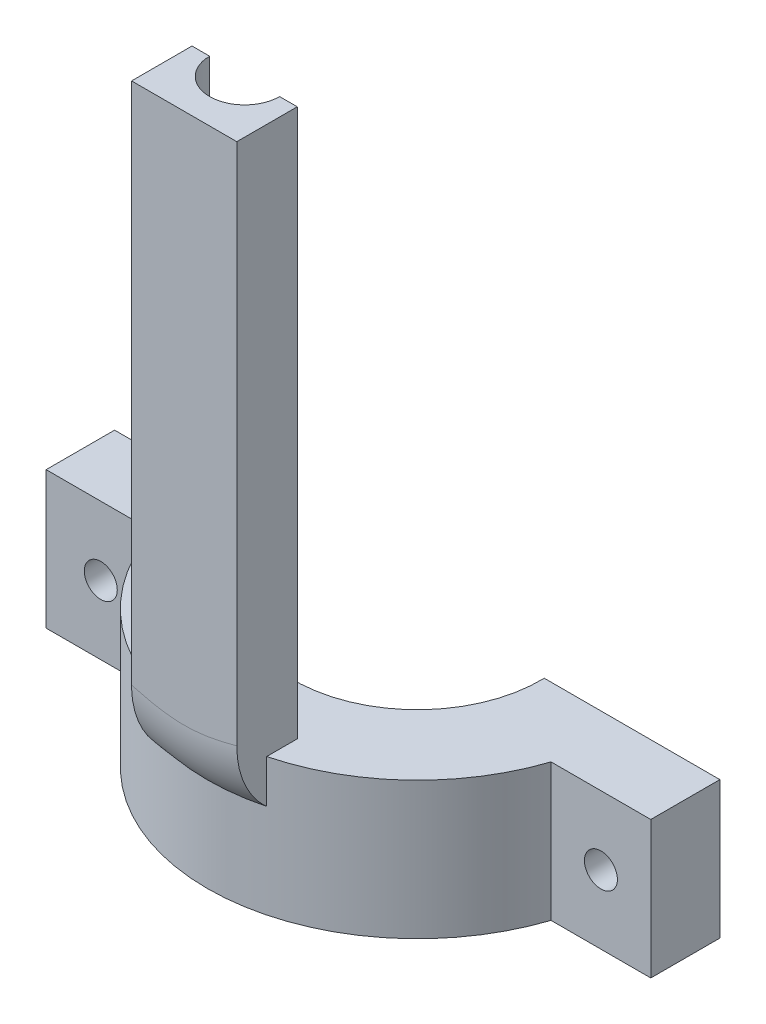
SolidWorks part; units mm, degrees
ref_plane "前基準面" through (0, 0, 0) normal (0, 0, 1) x (1, 0, 0)
ref_plane "上基準面" through (0, 0, 0) normal (0, 1, 0) x (1, 0, 0)
ref_plane "右基準面" through (0, 0, 0) normal (1, 0, 0) x (0, 0, -1)
sketch "草圖1" plane through (0, 0, 0) normal (0, 1, 0) x (1, 0, 0)
  circle A0 centre (0, 0) radius 14.32
  dimension "D1" = 28.64
extrude "伸長-薄件1" add sketch "草圖1" along normal blind 10 thin thin type one direction wall 10
ref_plane "平面1" through (0, 0, 25) normal (0, 0, 1) x (1, 0, 0)
sketch "草圖5" plane through (0, 0, 25) normal (0, 0, 1) x (1, 0, 0)
  line L0 (0, -990) -> (0, 49010) construction
  line L1 (14.32, 10) -> (-14.32, 10) construction
  line L2 (-1024.46, 5) -> (48975.54, 5) construction
  line L3 (-24.32, 10) -> (-24.32, 0) construction
  line L5 (-6.0941, 11.3789) -> (6.0941, 11.3789)
  line L6 (-6.0941, 11.3789) -> (-6.0941, 5)
  line L7 (-6.0941, 5) -> (6.0941, 5)
  line L8 (6.0941, 11.3789) -> (6.0941, 5)
  line L9 (-6.0941, 11.3789) -> (6.0941, 5) construction
  line L10 (-6.0941, 5) -> (6.0941, 11.3789) construction
  point P5 (0, 10)
  point P6 (0, 8.1895)
  point P10 (-24.32, 5)
  dimension "D1" = 0
extrude "填料-伸長3" add sketch "草圖5" along normal blind 5 and the other way blind 5
sketch "草圖6" plane through (0, 11.3789, 0) normal (0, 1, 0) x (1, 0, 0)
  line L1 (-6.0941, -20) -> (6.0941, -20)
  line L2 (-6.0941, -20) -> (-6.0941, -30)
  line L3 (-6.0941, -30) -> (6.0941, -30)
  line L4 (6.0941, -20) -> (6.0941, -30)
extrude "填料-伸長4" add sketch "草圖6" along normal blind 37
sketch "草圖8" plane through (0, 48.3789, 0) normal (0, 1, 0) x (1, 0, 0)
  line L1 (-6.0941, -30) -> (6.0941, -30)
  line L2 (-6.0941, -30) -> (-6.0941, -20)
  line L3 (-6.0941, -20) -> (6.0941, -20)
  line L4 (6.0941, -30) -> (6.0941, -20)
extrude "填料-伸長5" add sketch "草圖8" along normal blind 25.02
sketch "草圖9" plane through (0, 73.3989, 0) normal (0, 1, 0) x (1, 0, 0)
  line L0 (-6.0941, -20) -> (6.0941, -20) construction
  circle A0 centre (0, -20) radius 4.05
  dimension "D1" = 8.1
extrude "除料-伸長3" cut sketch "草圖9" against normal blind 24
ref_plane "平面2" through (25, 0, 0) normal (1, 0, 0) x (0, 0, -1)
sketch "草圖13" plane through (0, 73.3989, 0) normal (0, 1, 0) x (1, 0, 0)
  line L0 (6.0941, -30) -> (6.0941, -20) construction
  line L1 (-6.0941, -30) -> (6.0941, -30)
  line L2 (-6.0941, -30) -> (-6.0941, -27)
  line L3 (-6.0941, -27) -> (6.0941, -27)
  line L4 (6.0941, -30) -> (6.0941, -27)
  dimension "D1" = 3
extrude "除料-伸長4" cut sketch "草圖13" against normal through all
fillet "圓角1" radius 10 1 edges at (0, 5, 27)
sketch "草圖15" plane through (0, 0, 0) normal (0, -1, 0) x (1, 0, 0)
  circle A0 centre (0, 0) radius 14.32
extrude "伸長-薄件3" add sketch "草圖15" along normal blind 5.9 thin thin type one direction wall 10
sketch "草圖16" plane through (25, 0, 0) normal (1, 0, 0) x (0, 0, -1)
  line L0 (-975.68, 2.05) -> (49024.32, 2.05) construction
  line L1 (24.32, -5.9) -> (24.32, 10) construction
  line L2 (0.388, -990) -> (0.388, 49010) construction
  line L3 (24.32, 10) -> (-23.5441, 10) construction
  line L5 (-7.612, 10) -> (8.388, 10)
  line L6 (-7.612, 10) -> (-7.612, -5.9)
  line L7 (-7.612, -5.9) -> (8.388, -5.9)
  line L8 (8.388, 10) -> (8.388, -5.9)
  line L9 (-7.612, 10) -> (8.388, -5.9) construction
  line L10 (-7.612, -5.9) -> (8.388, 10) construction
  point P5 (24.32, 2.05)
  point P6 (0.388, 2.05)
  point P10 (0.388, 10)
  dimension "D1" = 0
  dimension "D2" = 16
extrude "填料-伸長7" add sketch "草圖16" along normal blind 9.65 and the other way blind 2
sketch "草圖17" plane through (0, 10, 0) normal (0, 1, 0) x (1, 0, 0)
  line L0 (23, 8.388) -> (34.65, 8.388) construction
  line L1 (23.2571, 8.388) -> (21.9049, 8.388)
  line L2 (23.2571, 8.388) -> (23.2571, 6.9951)
  line L3 (23.2571, 6.9951) -> (21.9049, 6.9951)
  line L4 (21.9049, 8.388) -> (21.9049, 6.9951)
extrude "填料-伸長8" add sketch "草圖17" against normal blind 15.8
sketch "草圖18" plane through (0, 0, 7.612) normal (0, 0, 1) x (1, 0, 0)
  line L0 (28.874, -990) -> (28.874, 49010) construction
  line L1 (23.098, 10) -> (34.65, 10) construction
  line L2 (-965.35, 2.05) -> (49034.65, 2.05) construction
  line L3 (34.65, 10) -> (34.65, -5.9) construction
  circle A0 centre (28.874, 2.05) radius 1.91
  point P5 (28.874, 10)
  point P10 (34.65, 2.05)
  dimension "D1" = 3.82
extrude "除料-伸長5" cut sketch "草圖18" against normal blind 24.8
ref_plane "平面3" through (-25, 0, 0) normal (1, 0, 0) x (0, 0, -1)
sketch "草圖19" plane through (-25, 0, 0) normal (1, 0, 0) x (0, 0, -1)
  line L0 (-975.68, 2.05) -> (49024.32, 2.05) construction
  line L1 (24.32, -5.9) -> (24.32, 10) construction
  line L2 (0.388, -990) -> (0.388, 49010) construction
  line L3 (24.32, 10) -> (-23.5441, 10) construction
  line L5 (8.4615, 10) -> (-7.5385, 10)
  line L6 (8.4615, 10) -> (8.4615, -5.9)
  line L7 (8.4615, -5.9) -> (-7.5385, -5.9)
  line L8 (-7.5385, 10) -> (-7.5385, -5.9)
  line L9 (8.4615, 10) -> (-7.5385, -5.9) construction
  line L10 (8.4615, -5.9) -> (-7.5385, 10) construction
  point P5 (24.32, 2.05)
  point P6 (0.4615, 2.05)
  point P10 (0.388, 10)
  dimension "D1" = 0
  dimension "D2" = 16
extrude "填料-伸長10" add sketch "草圖19" along normal blind 4.45 and the other way blind 10.45
sketch "草圖21" plane through (0, 0, -8.4615) normal (0, 0, -1) x (-1, 0, 0)
  line L0 (-977.1994, 2.05) -> (49022.8006, 2.05) construction
  line L1 (22.8006, -5.9) -> (22.8006, 10) construction
  line L2 (29.1253, -990) -> (29.1253, 49010) construction
  line L3 (35.45, 10) -> (22.8006, 10) construction
  circle A0 centre (29.1198, 2.05) radius 1.91
  point P5 (22.8006, 2.05)
  point P10 (29.1253, 10)
  dimension "D1" = 3.82
extrude "除料-伸長6" cut sketch "草圖21" against normal blind 35.45
sketch "草圖22" plane through (0, 10, 0) normal (0, 1, 0) x (1, 0, 0)
  line L0 (34.65, 8.388) -> (34.65, -7.612) construction
  line L1 (34.65, 0.388) -> (-42.8388, 0.388)
  line L2 (34.65, 0.388) -> (34.65, 26.9536)
  line L3 (34.65, 26.9536) -> (-42.8388, 26.9536)
  line L4 (-42.8388, 0.388) -> (-42.8388, 26.9536)
extrude "除料-伸長7" cut sketch "草圖22" against normal blind 35.45
